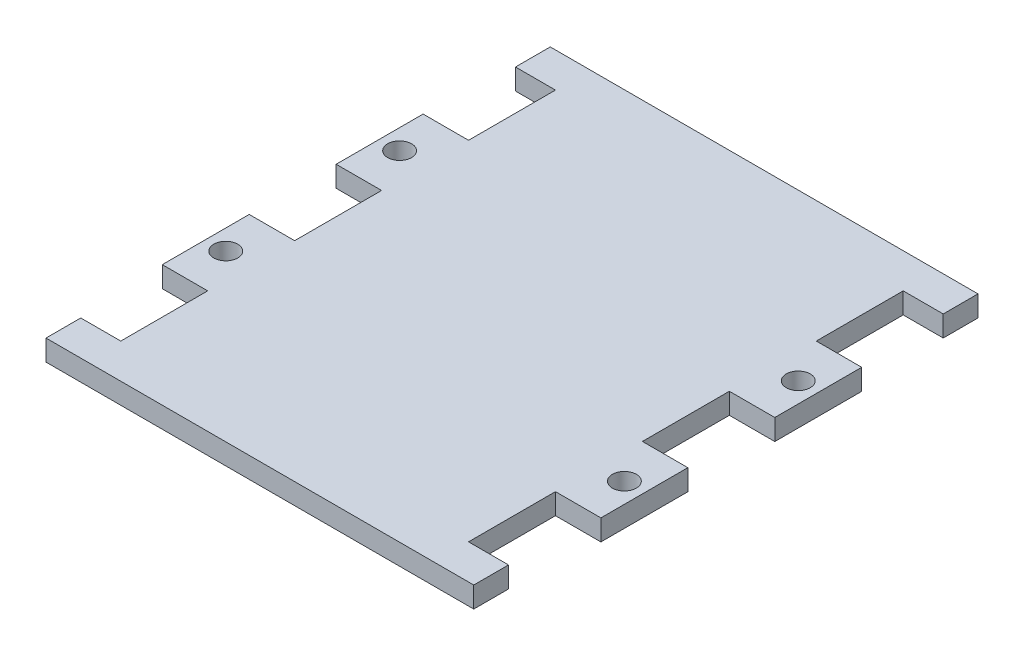
SolidWorks part; units mm, degrees
ref_plane "Front Plane" through (0, 0, 0) normal (0, 0, 1) x (1, 0, 0)
ref_plane "Top Plane" through (0, 0, 0) normal (0, 1, 0) x (1, 0, 0)
ref_plane "Right Plane" through (0, 0, 0) normal (1, 0, 0) x (0, 0, -1)
sketch "Sketch1" plane through (0, 0, 0) normal (0, 1, 0) x (1, 0, 0)
  line L0 (-31.242, -19.05) -> (-32.0358, -6.35) construction
  line L1 (31.242, -36.83) -> (-31.242, -36.83)
  line L2 (31.242, -36.83) -> (31.242, -31.75)
  line L3 (31.242, 36.83) -> (-31.242, 36.83)
  line L4 (-31.242, -36.83) -> (-31.242, -31.75)
  line L5 (0, 36.83) -> (0, -36.83) construction
  line L6 (31.242, 0) -> (-31.242, 0) construction
  line L7 (-25.4, -6.35) -> (-31.242, -6.35)
  line L8 (-25.4, -6.35) -> (-25.4, 6.35)
  line L9 (-25.4, 6.35) -> (-31.242, 6.35)
  line L10 (-25.4, -31.75) -> (-31.242, -31.75)
  line L11 (-28.321, 6.35) -> (-28.321, -6.35) construction
  line L12 (-25.4, 0) -> (-31.242, 0) construction
  line L13 (-25.4, -31.75) -> (-25.4, -19.05)
  line L14 (-25.4, -19.05) -> (-31.242, -19.05)
  line L15 (-28.321, -19.05) -> (-28.321, -31.75) construction
  line L16 (-25.4, -25.4) -> (-31.242, -25.4) construction
  line L17 (31.242, 6.35) -> (32.0358, 6.35)
  line L18 (-25.4, 25.4) -> (-31.242, 25.4) construction
  line L19 (-28.321, 19.05) -> (-28.321, 31.75) construction
  line L20 (-25.4, 19.05) -> (-31.242, 19.05)
  line L21 (-25.4, 31.75) -> (-25.4, 19.05)
  line L22 (-25.4, 31.75) -> (-31.242, 31.75)
  line L23 (-31.242, 31.75) -> (-31.242, 36.83)
  line L24 (-31.242, 12.7) -> (-25.4, 12.7) construction
  line L25 (28.321, 19.05) -> (28.321, 31.75) construction
  line L26 (25.4, 25.4) -> (31.242, 25.4) construction
  line L27 (25.4, -25.4) -> (31.242, -25.4) construction
  line L28 (28.321, -19.05) -> (28.321, -31.75) construction
  line L29 (25.4, 0) -> (31.242, 0) construction
  line L30 (28.321, 6.35) -> (28.321, -6.35) construction
  line L31 (25.4, 31.75) -> (31.242, 31.75)
  line L32 (25.4, 31.75) -> (25.4, 19.05)
  line L33 (25.4, 19.05) -> (31.242, 19.05)
  line L34 (25.4, -19.05) -> (31.242, -19.05)
  line L35 (25.4, -31.75) -> (25.4, -19.05)
  line L36 (25.4, -31.75) -> (31.242, -31.75)
  line L37 (25.4, 6.35) -> (31.242, 6.35)
  line L38 (25.4, -6.35) -> (25.4, 6.35)
  line L39 (25.4, -6.35) -> (31.242, -6.35)
  line L40 (31.242, 12.7) -> (25.4, 12.7) construction
  line L41 (31.242, 31.75) -> (31.242, 36.83)
  line L44 (-32.0358, -6.35) -> (-32.0358, -19.05)
  line L45 (-31.242, 19.05) -> (-32.0358, 19.05)
  line L46 (-31.242, -6.35) -> (-32.0358, -19.05) construction
  line L47 (-31.242, 6.35) -> (-32.0358, 6.35)
  line L48 (-32.0358, 19.05) -> (-32.0358, 6.35)
  line L49 (-31.242, 19.05) -> (-32.0358, 6.35) construction
  line L50 (-31.242, 6.35) -> (-32.0358, 19.05) construction
  line L51 (-31.242, -19.05) -> (-32.0358, -19.05)
  line L52 (-31.242, -6.35) -> (-32.0358, -6.35)
  line L53 (31.242, 6.35) -> (32.0358, 19.05) construction
  line L54 (31.242, 19.05) -> (32.0358, 6.35) construction
  line L55 (32.0358, 19.05) -> (32.0358, 6.35)
  line L56 (31.242, 19.05) -> (32.0358, 19.05)
  line L57 (31.242, -19.05) -> (32.0358, -19.05)
  line L58 (31.242, -6.35) -> (32.0358, -6.35)
  line L59 (31.242, -6.35) -> (32.0358, -19.05) construction
  line L60 (31.242, -19.05) -> (32.0358, -6.35) construction
  line L61 (32.0358, -6.35) -> (32.0358, -19.05)
  circle A0 centre (-29.1147, 12.7) radius 1.7526
  circle A1 centre (-29.1147, -12.7) radius 1.7526
  circle A2 centre (29.1147, -12.7) radius 1.7526
  circle A3 centre (29.1147, 12.7) radius 1.7526
  point P0 (0, 0)
  point P4 (-28.321, 0)
  point P9 (-28.321, -25.4)
  point P25 (-28.321, 25.4)
  point P67 (28.321, 25.4)
  point P68 (28.321, -25.4)
  point P69 (28.321, 0)
  point P76 (-31.6389, 12.7)
  dimension "D6" = 3.5052
  dimension "D1" = 62.484
  dimension "D2" = 73.66
  dimension "D3" = 5.842
  dimension "D4" = 12.7
  dimension "D7" = 0.7937
  dimension "D9" = 0.7937
  dimension "D5" = 2
  dimension "D8" = 2
  dimension "D10" = 2
extrude "Boss-Extrude1" add sketch "Sketch1" along normal blind 3.048
